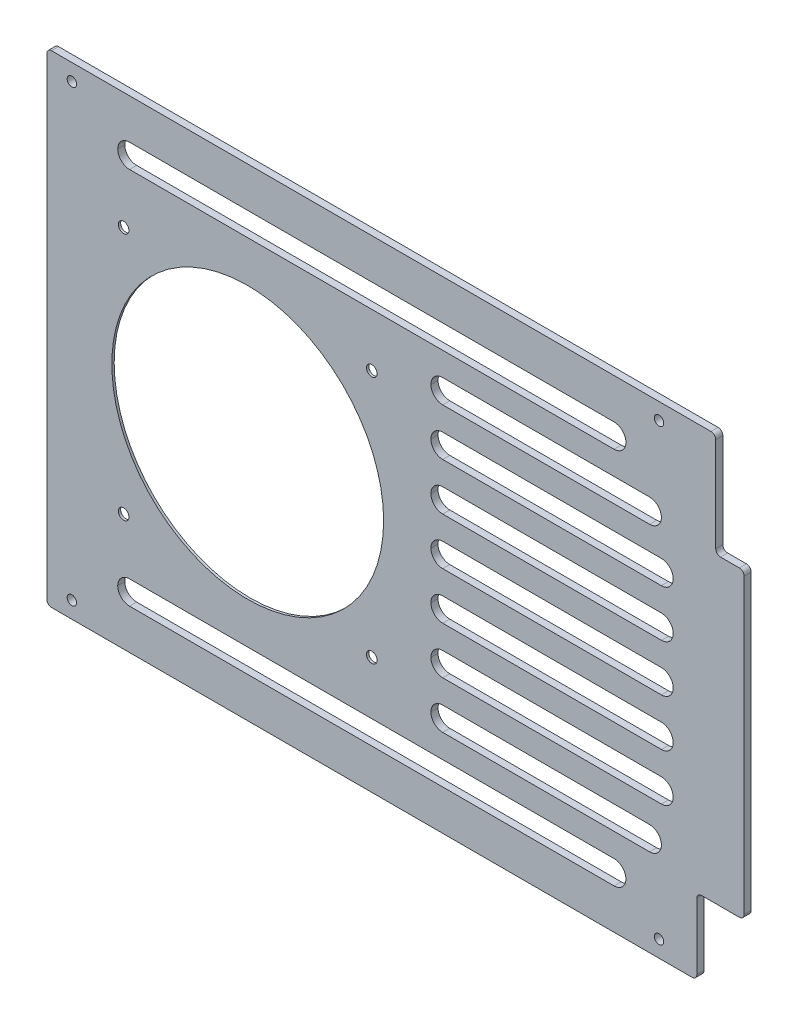
SolidWorks part; units mm, degrees
ref_plane "정면" through (0, 0, 0) normal (0, 0, 1) x (1, 0, 0)
ref_plane "윗면" through (0, 0, 0) normal (0, 1, 0) x (1, 0, 0)
ref_plane "우측면" through (0, 0, 0) normal (1, 0, 0) x (0, 0, -1)
sketch "스케치1" plane through (0, 0, 0) normal (0, 0, 1) x (1, 0, 0)
  line L1 (-137.5, -102) -> (137.5, -102)
  line L2 (-137.5, -102) -> (-137.5, 102)
  line L3 (-137.5, 102) -> (137.5, 102)
  line L4 (137.5, -102) -> (137.5, 102)
  line L5 (-137.5, -102) -> (137.5, 102) construction
  line L6 (-137.5, 102) -> (137.5, -102) construction
  line L7 (137.5, 102) -> (145.5, 102)
  line L8 (137.5, 102) -> (137.5, 58)
  line L9 (137.5, 58) -> (145.5, 58)
  line L10 (145.5, 102) -> (145.5, 58)
  line L11 (137.5, 58) -> (157.5, 58)
  line L12 (137.5, 58) -> (137.5, -70)
  line L13 (137.5, -70) -> (157.5, -70)
  line L14 (157.5, 58) -> (157.5, -70)
  point P0 (0, 0)
  dimension "D1" = 275
  dimension "D2" = 204
  dimension "D3" = 8
  dimension "D4" = 283
  dimension "D5" = 44
  dimension "D6" = 128
  dimension "D7" = 20
  dimension "D8" = 32
extrude "보스-돌출1" add sketch "스케치1" along normal blind 3 contours L1 L4 L3 L2 | L14 L11 L9 L4 L13 | L10 L7 L4 L9 region at (0, 0, 0) region at (147.5, -6, 0) region at (141.5, 80, 0)
sketch "스케치2" plane through (0, 0, 3) normal (0, 0, 1) x (1, 0, 0)
  line L0 (-137.5, 102) -> (145.5, 102) construction
  line L1 (-137.5, -102) -> (-137.5, 102) construction
  line L2 (145.5, 102) -> (145.5, 58) construction
  line L3 (-137.5, -102) -> (137.5, -102) construction
  line L4 (137.5, -102) -> (137.5, -70) construction
  line L6 (-105, 52.5) -> (0, 52.5)
  line L7 (-105, 52.5) -> (-105, -52.5)
  line L8 (-105, -52.5) -> (0, -52.5)
  line L9 (0, 52.5) -> (0, -52.5)
  line L10 (-105, 52.5) -> (0, -52.5) construction
  line L11 (-105, -52.5) -> (0, 52.5) construction
  circle A0 centre (-126.9, 95) radius 2
  circle A1 centre (121.5, 95) radius 2
  circle A2 centre (-126.9, -95) radius 2
  circle A3 centre (121.5, -95) radius 2
  circle A4 centre (-52.5, 0) radius 57.5
  circle A5 centre (-105, 52.5) radius 2.25
  circle A6 centre (0, 52.5) radius 2.25
  circle A7 centre (0, -52.5) radius 2.25
  circle A8 centre (-105, -52.5) radius 2.25
  point P34 (-52.5, 0)
  dimension "D1" = 4
  dimension "D4" = 4
  dimension "D7" = 4
  dimension "D10" = 4
  dimension "D14" = 102
  dimension "D16" = 115
  dimension "D19" = 4.5
  dimension "D2" = 7
  dimension "D3" = 10.6
  dimension "D5" = 24
  dimension "D6" = 7
  dimension "D8" = 7
  dimension "D9" = 10.6
  dimension "D11" = 16
  dimension "D12" = 7
  dimension "D13" = 85
  dimension "D15" = 102
  dimension "D17" = 105
  dimension "D18" = 105
  dimension "D20" = 4
extrude "컷-돌출1" cut sketch "스케치2" against normal blind 3 contours A0 | A8 | A7 | A6 | A5 | A4 | A2 | A3 | A1
sketch "스케치3" plane through (0, 0, 0) normal (0, 0, -1) x (-1, 0, 0)
  line L1 (-7.25, -59.75) -> (112.25, -59.75)
  line L2 (-7.25, -59.75) -> (-7.25, 59.75)
  line L3 (-7.25, 59.75) -> (112.25, 59.75)
  line L4 (112.25, -59.75) -> (112.25, 59.75)
  line L5 (-7.25, -59.75) -> (112.25, 59.75) construction
  line L6 (-7.25, 59.75) -> (112.25, -59.75) construction
  point P0 (52.5, 0)
  dimension "D1" = 119.5
  dimension "D2" = 119.5
extrude "컷-돌출2" cut sketch "스케치3" against normal blind 2 contours L2 L1 L4 L3
fillet "필렛1" radius 2 4 edges at (7.25, -59.75, 1) (-112.25, -59.75, 1) (-112.25, 59.75, 1) (7.25, 59.75, 1)
sketch "스케치4" plane through (0, 0, 3) normal (0, 0, 1) x (1, 0, 0)
  line L0 (-137.5, 0) -> (157.5, 0)
  line L1 (-137.5, -102) -> (-137.5, 102) construction
  line L2 (157.5, 58) -> (157.5, -70) construction
  line L3 (-137.5, 20) -> (157.5, 20)
  line L4 (-137.5, 40) -> (157.5, 40)
  line L5 (-137.5, 60) -> (157.5, 60)
  line L6 (-137.5, 80) -> (157.5, 80)
  line L7 (-137.5, -20) -> (157.5, -20)
  line L8 (-137.5, -40) -> (157.5, -40)
  line L9 (-137.5, -60) -> (157.5, -60)
  line L10 (-137.5, -80) -> (157.5, -80)
  point P3 (0, 0)
  point P16 (0, 0)
  dimension "D1" = 5
  dimension "D2" = 5
sketch "스케치5" plane through (0, 0, 3) normal (0, 0, 1) x (1, 0, 0)
  line L0 (-107.5, -80) -> (107.5, -80)
  line L1 (-137.5, -80) -> (157.5, -80) construction
  line L2 (-137.5, -102) -> (-137.5, 102) construction
  line L3 (137.5, -102) -> (137.5, -70) construction
  line L4 (25, -60) -> (122.5, -60)
  line L5 (-137.5, -60) -> (157.5, -60) construction
  line L7 (-137.5, 0) -> (157.5, 0) construction
  line L9 (157.5, 58) -> (157.5, -70) construction
  line L10 (25, -40) -> (127.5, -40)
  line L11 (-137.5, -40) -> (157.5, -40) construction
  line L12 (25, -20) -> (127.5, -20)
  line L13 (-137.5, -20) -> (157.5, -20) construction
  line L14 (127.5, 0) -> (25, 0)
  line L15 (25, 20) -> (127.5, 20)
  line L16 (25, 40) -> (127.5, 40)
  line L17 (25, 60) -> (122.5, 60)
  line L18 (-107.5, 80) -> (107.5, 80)
  dimension "D1" = 30
  dimension "D2" = 30
  dimension "D3" = 162.5
  dimension "D4" = 35
  dimension "D5" = 30
  dimension "D6" = 162.5
  dimension "D7" = 162.5
  dimension "D8" = 30
  dimension "D9" = 162.5
  dimension "D10" = 30
extrude "컷-돌출-얇게1" cut sketch "스케치5" against normal blind 3 thin thin type mid plane wall 10
fillet "필렛2" radius 5 36 edges at (107.5, -85, 1.5) (122.5, -65, 1.5) (127.5, -45, 1.5) (127.5, -25, 1.5) (127.5, -5, 1.5) (127.5, 15, 1.5) (127.5, 35, 1.5) (122.5, 55, 1.5) (107.5, 75, 1.5) (25, 65, 1.5) (25, 45, 1.5) (25, 25, 1.5) (25, 5, 1.5) (25, -15, 1.5) (25, -35, 1.5) (25, -55, 1.5) (-107.5, -75, 1.5) (25, -65, 1.5) (25, -45, 1.5) (25, -25, 1.5) (25, -5, 1.5) (25, 15, 1.5) (25, 35, 1.5) (25, 55, 1.5) (-107.5, -85, 1.5) (127.5, 5, 1.5) (127.5, -15, 1.5) (127.5, -35, 1.5) (122.5, -55, 1.5) (107.5, -75, 1.5) (127.5, 25, 1.5) (122.5, 65, 1.5) (127.5, 45, 1.5) (107.5, 85, 1.5) (-107.5, 75, 1.5) (-107.5, 85, 1.5)
fillet "필렛3" radius 2 8 edges at (-137.5, -102, 1.5) (137.5, -102, 1.5) (137.5, -70, 1.5) (157.5, -70, 1.5) (157.5, 58, 1.5) (145.5, 58, 1.5) (145.5, 102, 1.5) (-137.5, 102, 1.5)
